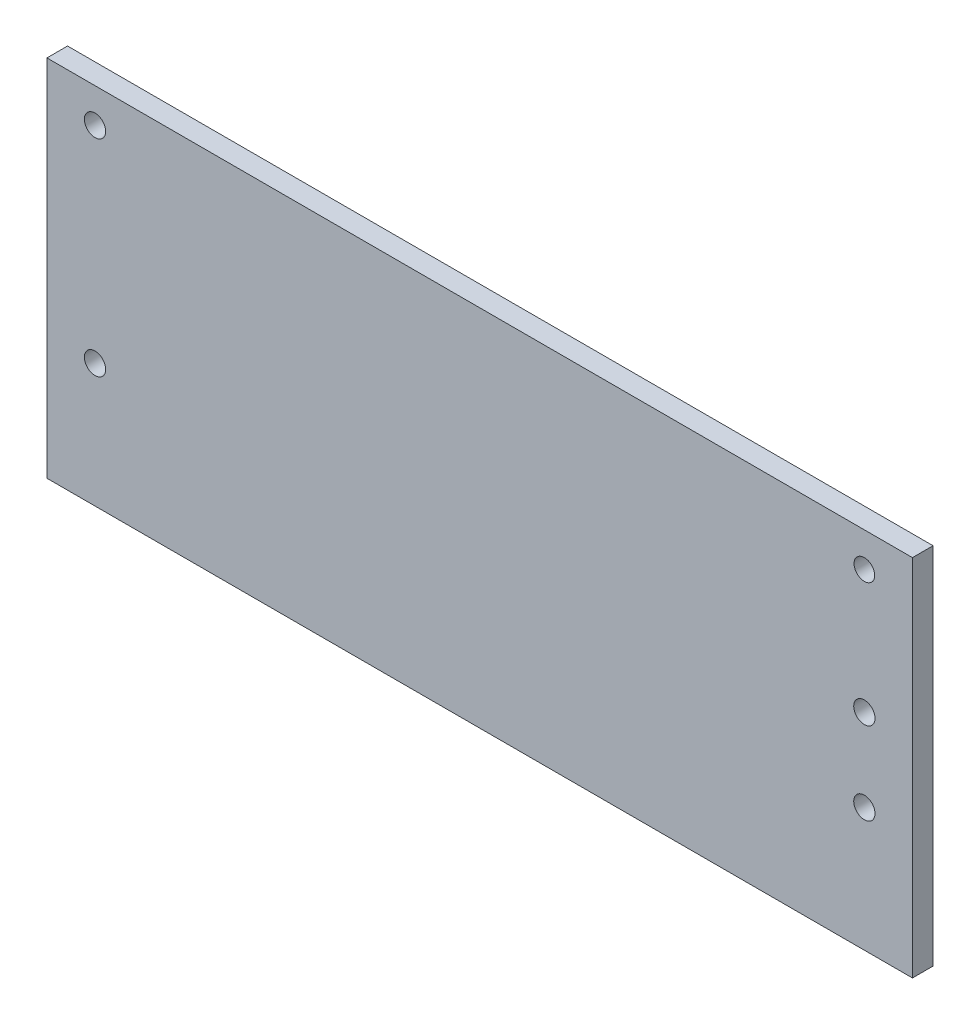
SolidWorks part; units mm, degrees
ref_plane "前视基准面" through (0, 0, 0) normal (0, 0, 1) x (1, 0, 0)
ref_plane "上视基准面" through (0, 0, 0) normal (0, 1, 0) x (1, 0, 0)
ref_plane "右视基准面" through (0, 0, 0) normal (1, 0, 0) x (0, 0, -1)
other "Configuration Table"
sketch "草图1" plane through (0, 0, 0) normal (0, 0, 1) x (1, 0, 0)
  line L1 (63, -26.5) -> (-63, -26.5)
  line L2 (63, -26.5) -> (63, 26.5)
  line L3 (63, 26.5) -> (-63, 26.5)
  line L4 (-63, -26.5) -> (-63, 26.5)
  line L5 (63, -26.5) -> (-63, 26.5) construction
  line L6 (63, 26.5) -> (-63, -26.5) construction
  point P0 (0, 0)
  dimension "D1" = 126
  dimension "D2" = 53
extrude "凸台-拉伸1" add sketch "草图1" along normal blind 3
sketch "草图2" plane through (0, 0, 0) normal (0, 0, -1) x (-1, 0, 0)
  line L0 (-63, 26.5) -> (63, 26.5) construction
  line L1 (-63, -26.5) -> (-63, 26.5) construction
  line L2 (63, 26.5) -> (63, -26.5) construction
  circle A0 centre (56, 21.5) radius 1.55
  circle A1 centre (-56, 21.5) radius 1.5
  dimension "D1" = 5
  dimension "D2" = 5
  dimension "D3" = 7
  dimension "D4" = 7
extrude "切除-拉伸1" cut sketch "草图2" against normal blind 10 contours A0 | A1
sketch "草图3" plane through (0, 0, 3) normal (0, 0, 1) x (1, 0, 0)
  line L0 (-56, 21.5) -> (-56, -8.5) construction
  line L1 (56, 21.5) -> (56, -8.5) construction
  circle A0 centre (-56, -8.5) radius 1.55
  circle A1 centre (56, -8.5) radius 1.55
  dimension "D1" = 3.1
  dimension "D2" = 3.1
  dimension "D3" = 30
extrude "切除-拉伸2" cut sketch "草图3" against normal blind 10
sketch "草图4" plane through (0, 0, 3) normal (0, 0, 1) x (1, 0, 0)
  line L0 (-56, 21.5) -> (-56, 3.5) construction
  line L1 (0, 0) -> (0, -11.8695) construction
  circle A0 centre (-56, 3.5) radius 1.55
  circle A1 centre (56, 3.5) radius 1.55
  dimension "D1" = 3.1
  dimension "D2" = 18
sketch "草图5" plane through (0, 0, 3) normal (0, 0, 1) x (1, 0, 0)
  circle A0 centre (56, 3.5) radius 1.55 construction
  circle A1 centre (56, 3.5) radius 1.55
extrude "切除-拉伸5" cut sketch "草图5" against normal blind 10
